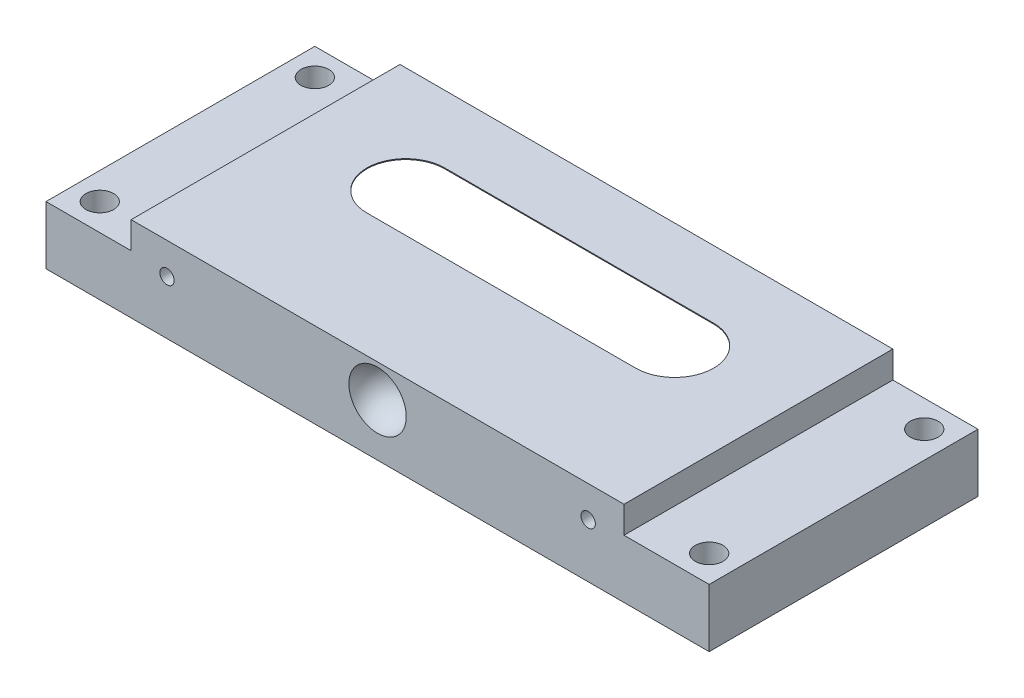
SolidWorks part; units mm, degrees
note: '?' marks a value the reader was unsure of. The reader was unsure of these and kept them because the rebuilt part matched: shared geometry of "Sketch12<8>".
material "6061 Alloy"
ref_plane "Front Plane" through (0, 0, 0) normal (0, 0, 1) x (1, 0, 0)
ref_plane "Top Plane" through (0, 0, 0) normal (0, 1, 0) x (1, 0, 0)
ref_plane "Right Plane" through (0, 0, 0) normal (1, 0, 0) x (0, 0, -1)
sketch "Sketch1" plane through (0, 0, 0) normal (0, 1, 0) x (1, 0, 0)
  line L1 (0, 0) -> (74, 0)
  line L2 (0, 0) -> (0, 30)
  line L3 (0, 30) -> (74, 30)
  line L4 (74, 0) -> (74, 30)
extrude "Boss-Extrude1" add sketch "Sketch1" along normal blind 9.5
sketch "Sketch2" plane through (0, 9.5, 0) normal (0, 1, 0) x (1, 0, 0)
  line L0 (0, 0) -> (74, 0) construction
  line L1 (74, 30) -> (64.5, 30)
  line L2 (74, 30) -> (74, 0)
  line L3 (74, 0) -> (64.5, 0)
  line L4 (64.5, 30) -> (64.5, 0)
  line L6 (0, 30) -> (9.5, 30)
  line L7 (0, 30) -> (0, 0)
  line L8 (0, 0) -> (9.5, 0)
  line L9 (9.5, 30) -> (9.5, 0)
extrude "Cut-Extrude1" cut sketch "Sketch2" against normal blind 3
ref_plane "Plane1" through (37, 0, 0) normal (1, 0, 0) x (0, 0, -1)
hole_wizard "CSK for M3 Flat Head Machine Screw1" positions "3DSketch1" profile "Sketch8" countersink size "M3" standard "ANSI Metric" end condition through all
sketch3d "3DSketch1"
  line L0 (0, 0, -30) -> (0, 0, 0) construction
  line L1 (74, 0, 0) -> (74, 0, -30) construction
  line L2 (74, 0, -30) -> (0, 0, -30) construction
  line L3 (0, 0, 0) -> (74, 0, 0) construction
  point P0 (3, 0, -3)
  point P2 (3, 0, -27)
  point P4 (71, 0, -27)
  point P6 (71, 0, -3)
  dimension "D1" = 3
  dimension "D2" = 3
  dimension "D3" = 3
  dimension "D4" = 3
sketch "Sketch8" plane through (3, 0, -3) normal (1, 0, 0) x (0, 0, -1)
  line L0 (0, 0) -> (0, 9.5)
  line L1 (0, 9.5) -> (1.55, 9.5)
  line L2 (1.55, 9.5) -> (1.55, 1.15)
  line L3 (1.55, 1.15) -> (2.7, 0)
  line L5 (2.7, 0) -> (0, 0)
  line L6 (-1.55, 1.15) -> (-2.7, 0) construction
  line L11 (0, -6.35) -> (0, 107.95) construction
  dimension "Thru Hole Dia." = 3.1
  dimension "Thru Hole Depth" = 9.5
  dimension "Near C'Sink Dia." = 5.4
  dimension "Near C'Sink Angle" = 90
ref_plane "Plane2" through (0, -11.5, 0) normal (0, -1, 0) x (-1, 0, 0)
sketch "Sketch12" plane through (0, -11.5, 0) normal (0, -1, 0) x (-1, 0, 0)
  line L0 (-37, 5.225) -> (-37, -5.225) construction
  line L1 (-52, -3.2) -> (-22, -3.2)
  line L2 (-52, -3.2) -> (-52, 39.5)
  line L3 (-52, 39.5) -> (-22, 39.5)
  line L4 (-22, -3.2) -> (-22, 39.5)
  line L5 (-52, -3.2) -> (-22, 39.5) construction
  line L6 (-52, 39.5) -> (-22, -3.2) construction
  arc A0 (-52, 39.5) -> (-52, -3.2) centre (-52, 18.15) ccw
  arc A1 (-22, -3.2) -> (-22, 39.5) centre (-22, 18.15) ccw
  point P0 (-37, 18.15)
  dimension "D1" = 3.2
  dimension "D2" = 42.7
  dimension "D3" = 30
ref_axis "Axis4" through (-3.2152, -11.5, -18.15) along (1, 0, 0)?
ref_axis "Axis5" through (52, -11.5, -39.5) along (0, 0, 1)?
ref_axis "Axis6" through (22, -11.5, -39.5) along (0, 0, 1)?
revolve "Cut-Revolve5" cut sketch "Sketch12" angle 360 about L2
revolve "Cut-Revolve6" cut sketch "Sketch12<8>" angle 360 about L4
sketch "Sketch12<8>" plane through (0, -11.5, 0) normal (0, -1, 0) x (-1, 0, 0) same geometry as "Sketch12"
sketch "Sketch13" plane through (0, -11.5, 0) normal (0, -1, 0) x (-1, 0, 0)
  line L0 (-52.7709, 18.15) -> (-21.7368, 18.15)
  line L1 (3.2152, 18.15) -> (-86.1354, 18.15) construction
sketch "Sketch14" plane through (0, -11.5, 0) normal (0, -1, 0) x (-1, 0, 0)
  line L1 (-52.7709, 18.15) -> (-21.7368, 18.15) construction
  line L2 (-52, 18.15) -> (-22, 18.15)
  line L3 (-52, 18.15) -> (-52, 39.5)
  line L4 (-52, 39.5) -> (-22, 39.5)
  line L5 (-22, 18.15) -> (-22, 39.5)
  line L7 (-74, 0) -> (-74, 30) construction
  dimension "D1" = 21.35
  dimension "D2" = 30
  dimension "D3" = 22
revolve "Cut-Revolve7" cut sketch "Sketch14" angle 360 about L2
ref_plane "Plane3" through (0, 0, 0) normal (0, 0, 1) x (1, 0, 0)
sketch "Sketch19" plane through (0, 0, 0) normal (0, 0, 1) x (1, 0, 0)
  line L0 (0, 6.5) -> (0, 0) construction
  line L1 (9.5, 9.5) -> (64.5, 9.5) construction
  point P0 (37, 5.8)
  dimension "D1" = 37
  dimension "D2" = 3.7
sketch "Sketch20" plane through (0, 0, 0) normal (0, 0, 1) x (1, 0, 0)
  line L0 (37, 9) -> (37, 2.6)
  circle A0 centre (37, 5.8) radius 3.2
revolve "Cut-Revolve8" cut sketch "Sketch20" angle 360 about L0
sketch "Sketch21" plane through (0, 0, 0) normal (0, 0, 1) x (1, 0, 0)
  line L0 (9.5, 9.5) -> (64.5, 9.5) construction
  line L1 (64.5, 6.5) -> (64.5, 9.5) construction
  line L2 (9.5, 6.5) -> (9.5, 9.5) construction
  circle A0 centre (13.5, 6) radius 0.8
  circle A1 centre (60.5, 6) radius 0.8
  point P0 (60.5, 6)
  point P1 (13.5, 6)
  dimension "D1" = 3.5
  dimension "D2" = 3.5
  dimension "D3" = 4
  dimension "D4" = 4
extrude "Cut-Extrude2" cut sketch "Sketch21" against normal blind 6
sketch "Sketch22" plane through (0, 0, 0) normal (0, 0, 1) x (1, 0, 0)
  line L0 (13.5, 6) -> (60.5, 6) construction
sketch "Sketch24" plane through (0, 0, -30) normal (0, 0, -1) x (-1, 0, 0)
  line L0 (-74, 6.5) -> (-64.5, 6.5) construction
  line L1 (-74, 6.5) -> (-74, 0) construction
  line L2 (0, 6.5) -> (0, 0) construction
  circle A0 centre (-67.5, 4.5) radius 1.5
  point P6 (-6.5, 4.5)
  dimension "D1" = 2
  dimension "D2" = 6.5
  dimension "D3" = 6.5
hole_wizard "Tap Drill for M3x0.5 Tap1" positions "3DSketch2" profile "Sketch25" hole size "M3x0.5" standard "ANSI Metric"
sketch3d "3DSketch2"
  point P0 (6.5, 4.5, -30)
  point P3 (67.5, 4.5, -30)
sketch "Sketch25" plane through (6.5, 4.5, -30) normal (1, 0, 0) x (0, 1, 0)
  line L0 (0, 0) -> (0, 5.2511)
  line L1 (0, 5.2511) -> (1.25, 4.5)
  line L2 (1.25, 4.5) -> (1.25, 0)
  line L5 (1.25, 0) -> (0, 0)
  line L10 (0, 5.2511) -> (-1.25, 4.5) construction
  line L11 (0, -6.35) -> (0, 107.95) construction
  dimension "Hole Dia." = 2.5
  dimension "Hole Depth" = 4.5
  dimension "Drill Angle" = 118
sketch "Sketch26" plane through (0, 9.5, 0) normal (0, 1, 0) x (1, 0, 0)
  line L32 (52, 13.8) -> (22, 13.8)
  line L33 (22, 22.5) -> (52, 22.5)
  line L34 (52, 13.8) -> (22, 13.8)
  line L35 (22, 22.5) -> (52, 22.5)
  arc A28 (52, 13.8) -> (52, 22.5) centre (52, 18.15) ccw
  arc A29 (52, 13.8) -> (52, 22.5) centre (52, 18.15) ccw
  arc A31 (22, 22.5) -> (22, 13.8) centre (22, 18.15) ccw
  arc A32 (22, 22.5) -> (22, 13.8) centre (22, 18.15) ccw
  dimension "D1" = 0.5
  dimension "D2" = 0.5
extrude "Cut-Extrude3" cut sketch "Sketch26" against normal blind 10
